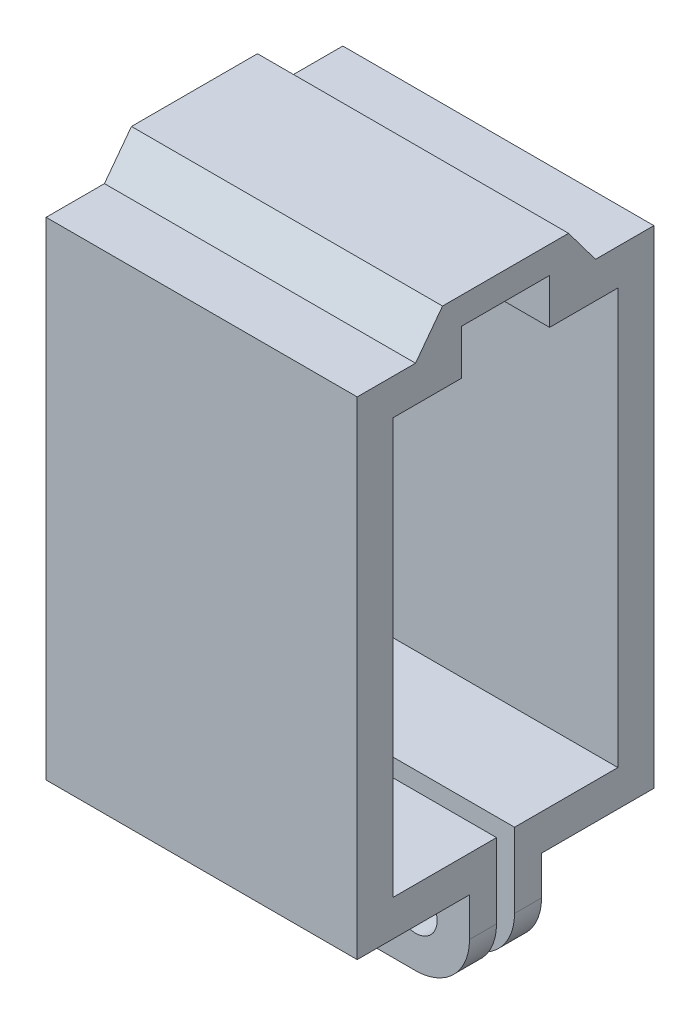
SolidWorks part; units mm, degrees
ref_plane "Front Plane" through (0, 0, 0) normal (0, 0, 1) x (1, 0, 0)
ref_plane "Top Plane" through (0, 0, 0) normal (0, 1, 0) x (1, 0, 0)
ref_plane "Right Plane" through (0, 0, 0) normal (1, 0, 0) x (0, 0, -1)
sketch "Sketch1" plane through (0, 0, 0) normal (1, 0, 0) x (0, 0, -1)
  line L0 (6.24, 6.24) -> (-6.24, 6.24)
  line L1 (-6.24, 6.24) -> (-6.24, -16.8311)
  line L2 (-6.24, -16.8311) -> (6.24, -16.8311)
  line L3 (6.24, -16.8311) -> (6.24, 6.24)
  line L4 (6.09, 6.09) -> (-6.09, 6.09)
  line L5 (-6.09, 6.09) -> (-6.09, -16.6811)
  line L6 (-6.09, -16.6811) -> (6.09, -16.6811)
  line L7 (6.09, -16.6811) -> (6.09, 6.09)
  line L8 (6.09, 6.09) -> (-6.09, 6.09) construction
  line L9 (-6.09, 6.09) -> (-6.09, -16.6811) construction
  line L10 (-6.09, -16.6811) -> (6.09, -16.6811) construction
  line L11 (6.09, -16.6811) -> (6.09, 6.09) construction
  line L12 (8.24, 8.24) -> (-8.24, 8.24)
  line L13 (-8.24, 8.24) -> (-8.24, -18.8311)
  line L14 (-8.24, -18.8311) -> (8.24, -18.8311)
  line L15 (8.24, -18.8311) -> (8.24, 8.24)
  dimension "D1" = 0
  dimension "D2" = 0.15
  dimension "D3" = 2
extrude "Boss-Extrude1" add sketch "Sketch1" along normal offset from surface (17.2796 mm away) 0.5 offset beyond the face yes
sketch "Sketch2" plane through (17.2796, 0, 0) normal (1, 0, 0) x (0, 0, -1)
  line L0 (8.24, 8.24) -> (-8.24, 8.24) construction
  line L1 (-5, 8.24) -> (5, 8.24)
  line L3 (-3.5, 10.24) -> (3.5, 10.24)
  line L5 (-5, 8.24) -> (-3.5, 10.24)
  line L6 (5, 8.24) -> (3.5, 10.24)
  line L7 (0, 10.24) -> (0, 8.24) construction
  point P6 (0, 8.24)
  dimension "D1" = 2
  dimension "D2" = 7
  dimension "D3" = 10
extrude "Boss-Extrude2" add sketch "Sketch2" against normal up to surface (17.2796 mm away) up to face at (0, -5.2956, 0)
sketch "Sketch3" plane through (17.2796, 0, 0) normal (1, 0, 0) x (0, 0, -1)
  line L0 (-1.4478, 7.74) -> (1.4478, 7.74) construction
  line L1 (-2.4478, 5.09) -> (2.4478, 5.09)
  line L2 (2.4478, 5.09) -> (2.4478, 8.74)
  line L3 (-2.4478, 8.74) -> (2.4478, 8.74)
  line L4 (-1.4478, 6.09) -> (1.4478, 6.09)
  line L5 (1.4478, 6.09) -> (1.4478, 12.186)
  line L6 (1.4478, 12.186) -> (-1.4478, 12.186)
  line L7 (-1.4478, 12.186) -> (-1.4478, 6.09)
  line L8 (-1.4478, 6.09) -> (1.4478, 6.09) construction
  line L9 (1.4478, 6.09) -> (1.4478, 7.74) construction
  line L11 (-1.4478, 7.74) -> (-1.4478, 6.09) construction
  line L12 (-2.4478, 8.74) -> (-2.4478, 5.09)
  line L13 (3.5, 10.24) -> (-3.5, 10.24) construction
  dimension "D2" = 1
  dimension "D3" = 1.5
  dimension "D1" = 0
extrude "Cut-Extrude1" cut sketch "Sketch3" against normal through all
sketch "Sketch4" plane through (17.2796, 0, 0) normal (1, 0, 0) x (0, 0, -1)
  line L0 (-8.24, -18.8311) -> (8.24, -18.8311) construction
  line L1 (-2, -18.8311) -> (2, -18.8311)
  line L2 (-2, -18.8311) -> (-2, -23.9811)
  line L3 (-2, -23.9811) -> (2, -23.9811)
  line L4 (2, -18.8311) -> (2, -23.9811)
  point P6 (0, -18.8311)
  dimension "D1" = 5.15
  dimension "D2" = 4
extrude "Boss-Extrude3" add sketch "Sketch4" against normal up to surface (17.2796 mm away) up to face at (0, 1.9722, 0)
sketch "Sketch5" plane through (17.2796, 0, 0) normal (1, 0, 0) x (0, 0, -1)
  line L0 (-6.24, -16.8311) -> (6.24, -16.8311) construction
  line L1 (-0.5, -16.8311) -> (0.5, -16.8311)
  line L2 (-0.5, -16.8311) -> (-0.5, -23.9811)
  line L3 (-0.5, -23.9811) -> (0.5, -23.9811)
  line L4 (0.5, -16.8311) -> (0.5, -23.9811)
  line L5 (-2, -23.9811) -> (2, -23.9811) construction
  point P8 (0, -16.8311)
  dimension "D1" = 1
fillet "Fillet1" radius 3 2 edges at (0, -23.9811, 0) (17.2796, -23.9811, 0)
extrude "Cut-Extrude3" cut sketch "Sketch5" against normal through all
hole_wizard "M2 Clearance Hole1" positions "Sketch6" profile "Sketch7" hole size "M2" standard "ANSI Metric" end condition through all
sketch "Sketch6" plane through (0, 0, -2) normal (0, 0, -1) x (-1, 0, 0)
  point P0 (-14.2796, -20.9811)
  point P3 (-3, -20.9811)
sketch "Sketch7" plane through (14.2796, -20.9811, -2) normal (1, 0, 0) x (0, 1, 0)
  line L0 (0, 0) -> (0, 10.24)
  line L1 (0, 10.24) -> (1.2, 10.24)
  line L2 (1.2, 10.24) -> (1.2, 0)
  line L5 (1.2, 0) -> (0, 0)
  line L11 (0, -6.35) -> (0, 107.95) construction
  dimension "Thru Hole Dia." = 2.4
  dimension "Thru Hole Depth" = 10.24
